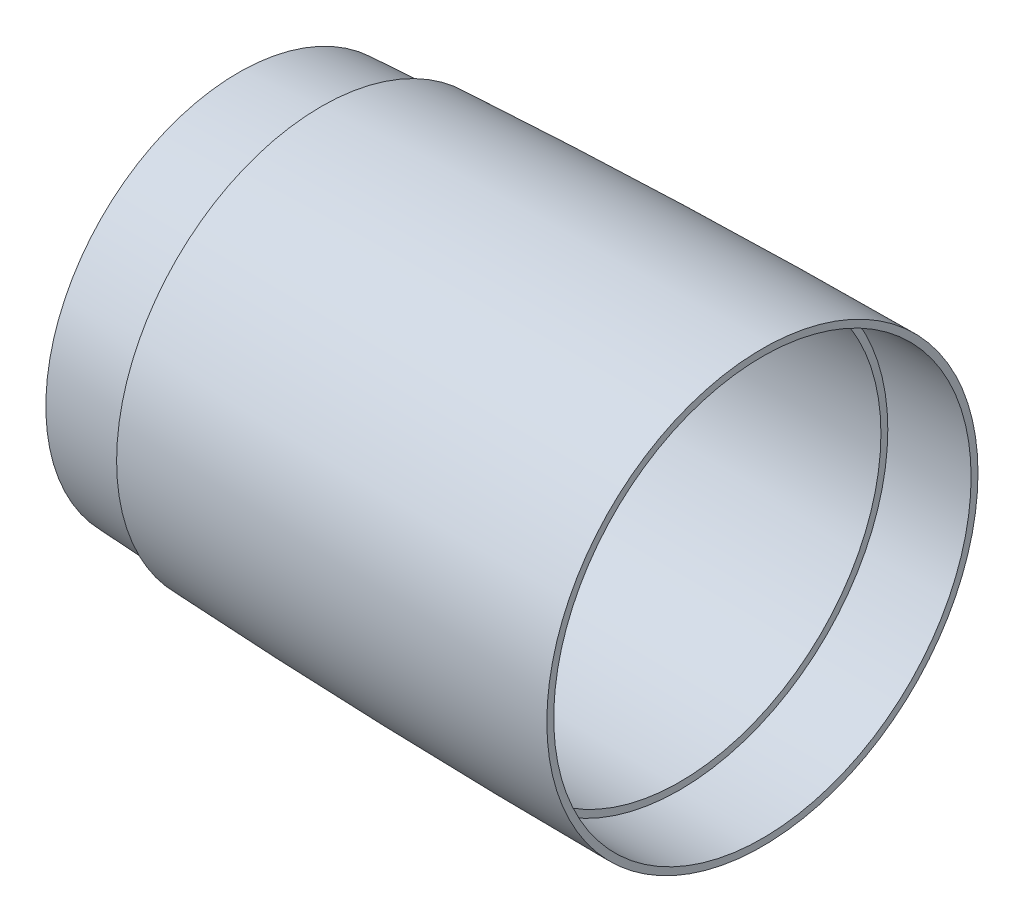
SolidWorks part; units mm, degrees
material "Thornel Mat VMA"
ref_plane "Front Plane" through (0, 0, 0) normal (0, 0, 1) x (1, 0, 0)
ref_plane "Top Plane" through (0, 0, 0) normal (0, 1, 0) x (1, 0, 0)
ref_plane "Right Plane" through (0, 0, 0) normal (1, 0, 0) x (0, 0, -1)
sketch "Sketch1" plane through (0, 0, 0) normal (0, 0, 1) x (1, 0, 0)
  line L0 (0, 0) -> (0, 3483.1) construction
  line L1 (0, 3635.5) -> (0, 3632.5)
  line L2 (0, 3557.2968) -> (-750, 3557.2968) construction
  line L3 (0, 3632.5) -> (0, 3635.5) construction
  line L4 (0, 3632.5) -> (160, 3632.5)
  line L5 (-5, 3627.5) -> (160, 3627.5)
  line L6 (-5, 3630.4966) -> (-5, 3627.5)
  line L7 (-750, 3557.2968) -> (-725.3758, 3557.2968)
  line L8 (160, 3632.5) -> (160, 3627.5)
  line L9 (-650, 3576.9205) -> (-650, 3571.8385)
  line L10 (-650, 3571.8385) -> (-600, 3571.8385)
  line L11 (-600, 3571.8385) -> (-600, 3580.5768)
  line L12 (-2.5, 3630) -> (157.5, 3630) construction
  line L13 (-2.5, 3630) -> (157.5, 3630) construction
  line L14 (-725.628, 3559.7968) -> (-725.628, 3559.7968)
  line L15 (-500, 3598.4287) -> (-500, 3595.9046)
  line L18 (157.5, 3630) -> (157.5, 3630)
  line L21 (-2.5, 3632.9991) -> (-2.5, 3630) construction
  line L22 (-2.5, 3632.9991) -> (-2.5, 3630) construction
  line L23 (-470, 3604.991) -> (-470, 3602.4698)
  line L24 (-320, 3621.3893) -> (-320, 3618.8795)
  line L25 (-350, 3616.1014) -> (-350, 3613.5897)
  line L26 (-40, 3632.7798) -> (-40, 3630.2796)
  line L27 (-10, 3632.9862) -> (-10, 3635.4862)
  line L28 (-170, 3629.0204) -> (-170, 3631.5231)
  line L29 (-200, 3627.4907) -> (-200, 3624.9869)
  line L30 (-40, 3630.2796) -> (-40, 3627.5)
  line L31 (-40, 3627.5) -> (-5, 3627.5)
  line L32 (-10, 3632.9862) -> (-10, 3632.6862)
  line L33 (-170, 3629.0204) -> (-170, 3628.7201)
  line L34 (-320, 3618.8795) -> (-320, 3618.5784)
  line L35 (-470, 3602.4698) -> (-470, 3602.1673)
  arc A0 (0, 3635.5) -> (-750, 3557.2968) centre (0, 0) ccw
  arc A1 (-5, 3630.4966) -> (-600, 3580.5768) centre (0, 0) ccw
  arc A2 (-5, 3630.4966) -> (-748.9685, 3552.4043) centre (0, 0) ccw construction
  arc A5 (-650, 3571.8385) -> (-725.3758, 3557.2968) centre (0, 0) ccw
  arc A6 (-5, 3630.4966) -> (-725.3758, 3557.2968) centre (0, 0) ccw construction
  arc A7 (-2.5, 3632.9991) -> (-725.628, 3559.7968) centre (0, 0) ccw construction
  arc A8 (-2.5, 3632.9991) -> (-725.628, 3559.7968) centre (0, 0) ccw construction
  arc A9 (-500, 3598.4287) -> (-470, 3602.4698) centre (0, 0) cw
  arc A10 (-350, 3616.1014) -> (-320, 3618.8795) centre (0, 0) cw
  arc A11 (-10, 3632.9862) -> (-40, 3632.7798) centre (0, 0) ccw
  arc A12 (-170, 3629.0204) -> (-200, 3627.4907) centre (0, 0) ccw
  arc A13 (-40, 3632.4798) -> (-10, 3632.6862) centre (0, 0) cw
  arc A14 (-200, 3627.1903) -> (-170, 3628.7201) centre (0, 0) cw
  arc A15 (-350, 3615.8) -> (-320, 3618.5784) centre (0, 0) cw
  arc A16 (-500, 3598.1258) -> (-470, 3602.1673) centre (0, 0) cw
  dimension "D1" = 7271
  dimension "D7" = 100
  dimension "D10" = 30
  dimension "D8" = 3633
  dimension "D12" = 3633
  dimension "D15" = 3633
  dimension "D18" = 3633
  dimension "D21" = 3632.7
  dimension "D23" = 3632.7
  dimension "D22" = 3632.7
  dimension "D24" = 3632.7
  dimension "D2" = 152.4
  dimension "D3" = 750
  dimension "D4" = 3
  dimension "D5" = 160
  dimension "D9" = 50
  dimension "D11" = 180
  dimension "D13" = 30
  dimension "D14" = 180
  dimension "D16" = 30
  dimension "D17" = 200
  dimension "D19" = 30
  dimension "D20" = 180
  dimension "D6" = 5
revolve "Revolve1" add sketch "Sketch1" angle 360 about L2 region at (-104.108, 3631.191, 0)
